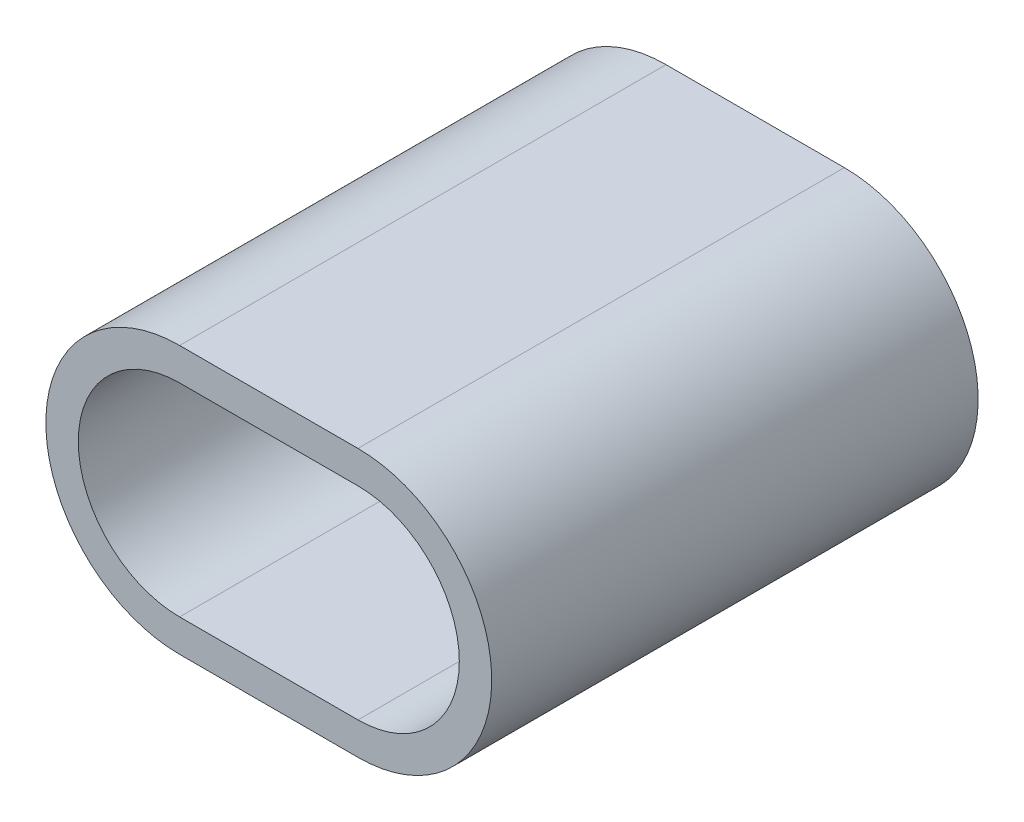
SolidWorks part; units mm, degrees
ref_plane "Front" through (0, 0, 0) normal (0, 0, 1) x (1, 0, 0)
ref_plane "Top" through (0, 0, 0) normal (0, 1, 0) x (1, 0, 0)
ref_plane "Right" through (0, 0, 0) normal (1, 0, 0) x (0, 0, -1)
sketch "Esquisse1" plane through (0, 0, 0) normal (0, 0, 1) x (1, 0, 0)
  line L0 (0, 0) -> (22, 0) construction
  line L1 (0, 16.5) -> (22, 16.5)
  line L2 (0, -16.5) -> (22, -16.5)
  arc A0 (0, 16.5) -> (0, -16.5) centre (0, 0) ccw
  arc A1 (22, -16.5) -> (22, 16.5) centre (22, 0) ccw
  point P3 (11, 0)
  dimension "D1" = 22
  dimension "D2" = 33
extrude "Boss.-Extru.1" add sketch "Esquisse1" along normal blind 4
sketch "Esquisse2" plane through (0, 0, 4) normal (0, 0, 1) x (1, 0, 0)
  line L0 (0, 0) -> (22, 0) construction
  line L1 (0, 16.5) -> (22, 16.5)
  line L2 (0, -16.5) -> (22, -16.5)
  line L3 (0, 0) -> (22, 0) construction
  line L4 (0, 12.5) -> (22, 12.5)
  line L5 (0, -12.5) -> (22, -12.5)
  arc A0 (0, 16.5) -> (0, -16.5) centre (0, 0) ccw
  arc A1 (22, -16.5) -> (22, 16.5) centre (22, 0) ccw
  arc A2 (0, 12.5) -> (0, -12.5) centre (0, 0) ccw
  arc A3 (22, -12.5) -> (22, 12.5) centre (22, 0) ccw
  point P3 (11, 0)
  point P10 (11, 0)
  dimension "D2" = 16.5
  dimension "D1" = 22
  dimension "D3" = 25
extrude "Boss.-Extru.2" add sketch "Esquisse2" along normal blind 56
sketch "Esquisse3" plane through (0, 0, 0) normal (0, 0, -1) x (-1, 0, 0)
  circle A0 centre (-4.5, -3) radius 1.5
  circle A1 centre (-19.5, -3) radius 1.5
  circle A2 centre (-19.5, 7) radius 1.5
  circle A3 centre (-4.5, 7) radius 1.5
  circle A4 centre (-19.5, 7) radius 1.5 construction
  circle A5 centre (-19.5, -3) radius 1.5 construction
  circle A6 centre (-4.5, 7) radius 1.5 construction
  circle A7 centre (-4.5, -3) radius 1.5 construction
  dimension "D1" = 3
  dimension "D2" = 3
  dimension "D3" = 3
  dimension "D4" = 3
  dimension "D5" = 0
  dimension "D6" = 0
  dimension "D7" = 0
  dimension "D8" = 0
extrude "Enlèv. mat.-Extru.1" cut sketch "Esquisse3" against normal through all
sketch "Esquisse4" plane through (0, 0, 4) normal (0, 0, 1) x (1, 0, 0)
  circle A0 centre (4.5, 7) radius 2.5
  circle A1 centre (19.5, 7) radius 2.5
  circle A2 centre (19.5, -3.1333) radius 2.5
  circle A3 centre (4.5, -3) radius 2.5
  dimension "D1" = 5
  dimension "D2" = 5
  dimension "D3" = 5
  dimension "D4" = 5
extrude "Enlèv. mat.-Extru.2" cut sketch "Esquisse4" against normal blind 3
fillet "Congé1" radius 2 4 edges at (22, 7, 1) (22, -3.1333, 1) (7, -3, 1) (7, 7, 1)
